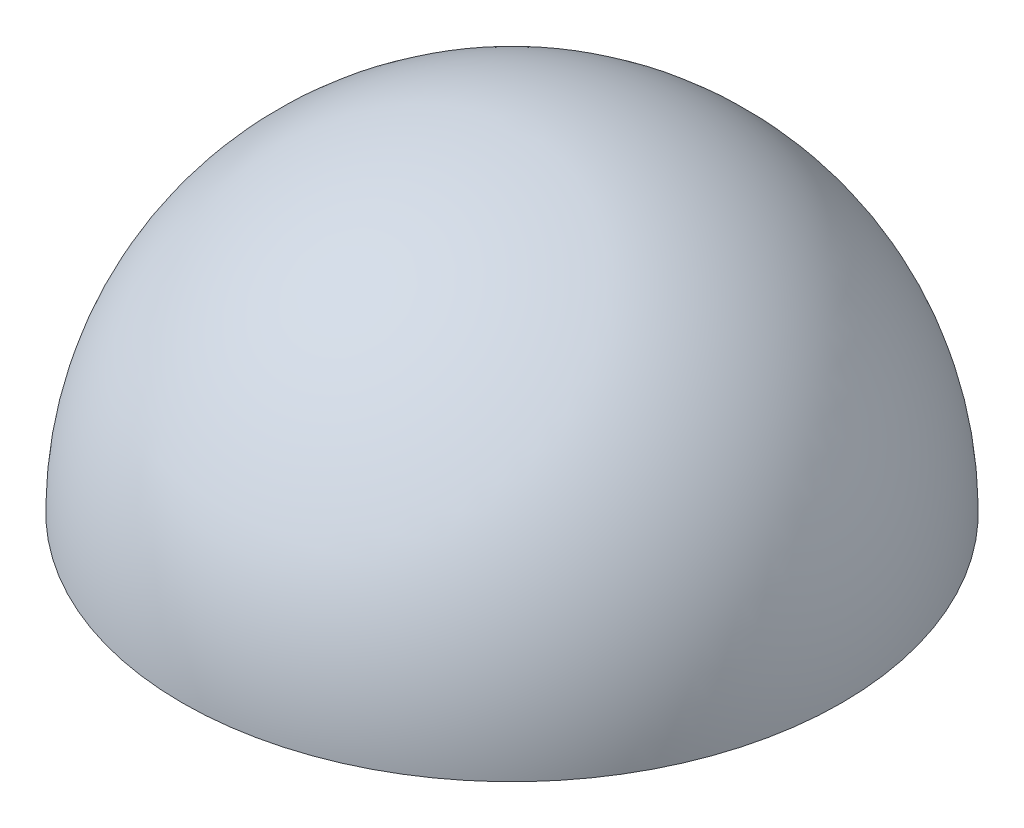
SolidWorks part; units mm, degrees
ref_plane "Front Plane" through (0, 0, 0) normal (0, 0, 1) x (1, 0, 0)
ref_plane "Top Plane" through (0, 0, 0) normal (0, 1, 0) x (1, 0, 0)
ref_plane "Right Plane" through (0, 0, 0) normal (1, 0, 0) x (0, 0, -1)
sketch "Sketch8" plane through (0, 0, 0) normal (0, 0, 1) x (1, 0, 0)
  line L0 (0, -5) -> (0, 0) construction
  line L2 (0, 5) -> (0, -5)
  arc A1 (0, -5) -> (0, 5) centre (0, 0) ccw
  dimension "D1" = 5
revolve "Revolve5" add sketch "Sketch8" angle 360 about L0 reverse direction yes
sketch "Sketch9" plane through (0, 0, 0) normal (0, 1, 0) x (1, 0, 0)
  circle A0 centre (0, 0) radius 5
  dimension "D1" = 10
extrude "Cut-Extrude1" cut sketch "Sketch9" against normal blind 5
